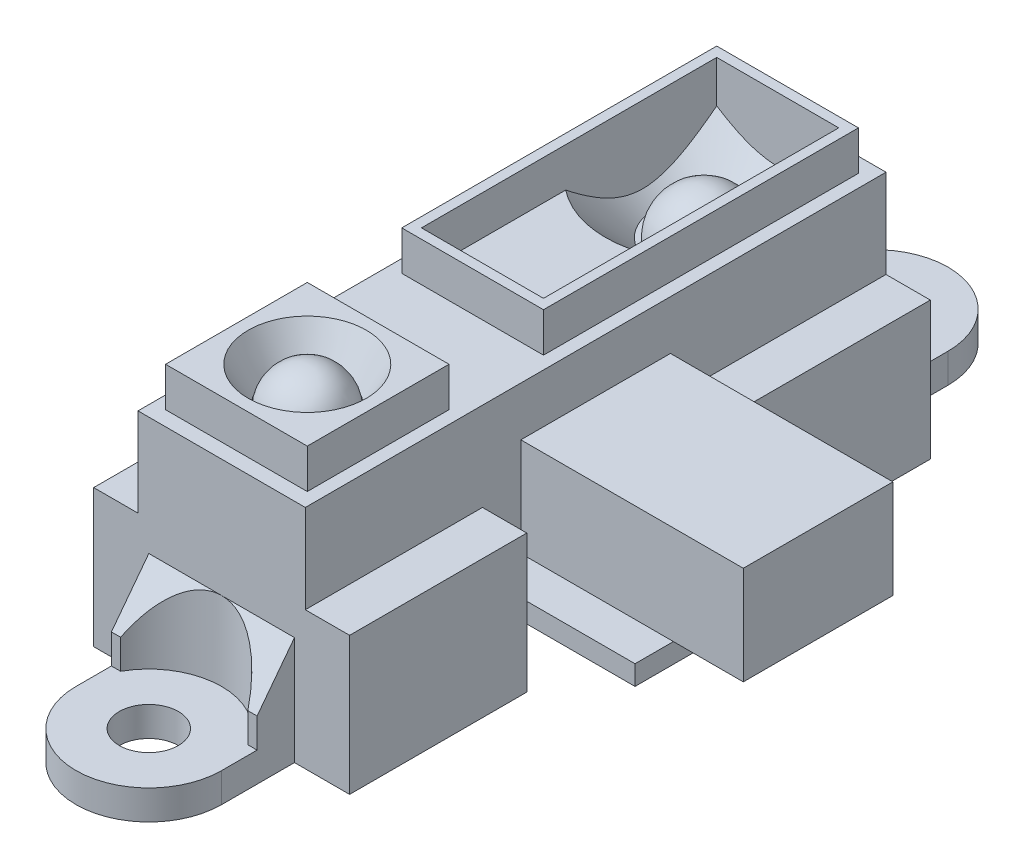
SolidWorks part; units mm, degrees
ref_plane "Спереди" through (0, 0, 0) normal (0, 0, 1) x (1, 0, 0)
ref_plane "Сверху" through (0, 0, 0) normal (0, 1, 0) x (1, 0, 0)
ref_plane "Справа" through (0, 0, 0) normal (1, 0, 0) x (0, 0, -1)
sketch "Эскиз1" plane through (0, 0, 0) normal (0, 1, 0) x (1, 0, 0)
  line L0 (0, 0) -> (13, 0)
  line L1 (13, 0) -> (13, 29.5)
  line L2 (13, 29.5) -> (0, 29.5)
  line L3 (0, 29.5) -> (0, 0)
extrude "Бобышка-Вытянуть1" add sketch "Эскиз1" along normal blind 7
sketch "Эскиз2" plane through (0, 7, 0) normal (0, 1, 0) x (1, 0, 0)
  line L0 (6.5, 29.5) -> (10.75, 29.5)
  line L1 (13, 29.5) -> (0, 29.5) construction
  line L2 (6.5, 29.5) -> (2.25, 29.5)
  line L3 (2.25, 29.5) -> (2.25, 0)
  line L4 (0, 0) -> (13, 0) construction
  line L5 (2.25, 0) -> (10.75, 0)
  line L6 (10.75, 0) -> (10.75, 29.5)
extrude "Бобышка-Вытянуть2" add sketch "Эскиз2" along normal blind 4.5
ref_plane "Плоскость1" through (6.5, 0, 0) normal (-1, 0, 0) x (0, 0, 1)
sketch "Эскиз5" plane through (6.5, 0, 0) normal (1, 0, 0) x (0, 0, -1)
  line L0 (29.5, 11.5) -> (24.5, 11.5)
  line L1 (0, 11.5) -> (29.5, 11.5) construction
  line L2 (24.5, 11.5) -> (24.5, 9) construction
  line L3 (24.5, 11.5) -> (24.5, 9) construction
  line L4 (26.75, 9) -> (27, 9)
  line L5 (24.5, 11.25) -> (24.5, 11.5)
  line L7 (27, 9) -> (29.5, 11.5)
  arc A0 (26.75, 9) -> (24.5, 11.25) centre (24.5, 9) ccw
  dimension "D1" = 5
revolve "Вырез-Повернуть2" cut sketch "Эскиз5" angle 360 about L2
sketch "Эскиз3" plane through (0, 11.5, 0) normal (0, 1, 0) x (1, 0, 0)
  line L1 (2.9, 7.95) -> (10.1, 0.75) construction
  line L2 (6.5, 29.5) -> (6.5, 28.75)
  line L3 (2.25, 0) -> (10.75, 0) construction
  line L4 (10.1, 7.95) -> (2.9, 0.75) construction
  line L5 (7.15, 20.75) -> (3.4, 20.75) construction
  line L6 (10.1, 0.75) -> (2.9, 0.75)
  line L7 (6.5, 6.325) -> (6.5, -6.325) construction
  line L10 (3.4, 20.75) -> (3.4, 28.25)
  line L11 (10.1, 12.75) -> (10.1, 28.75)
  line L12 (10.1, 0.75) -> (10.1, 0) construction
  line L13 (3.4, 28.25) -> (9.6, 28.25)
  line L14 (9.6, 28.25) -> (9.6, 13.25)
  line L15 (9.6, 13.25) -> (3.4, 13.25)
  line L16 (3.4, 13.25) -> (3.4, 20.75)
  line L17 (10.1, 0.75) -> (10.1, 7.95)
  line L18 (10.1, 7.95) -> (2.9, 7.95)
  line L19 (2.9, 7.95) -> (2.9, 0.75)
  line L20 (6.5, 29.5) -> (2.25, 29.5) construction
  line L21 (10.1, 28.75) -> (2.9, 28.75)
  line L22 (2.9, 28.75) -> (2.9, 12.75)
  line L23 (2.9, 12.75) -> (10.1, 12.75)
  circle A0 centre (6.5, 4.35) radius 2
  arc M19 (10.75, 21.8661) -> (2.25, 21.8661) centre (6.5, 24.5) cw
  dimension "D1" = 7.2
  dimension "D2" = 7.2
  dimension "D3" = 0.75
  dimension "D4" = 16
extrude "Бобышка-Вытянуть3" add sketch "Эскиз3" along normal blind 2 contours L22 L23 L11 L14 L15 L16 M19 | L21 L22 L16 L10 L13 L14 L11 M19 | L18 L19 L6 L17 A0 region at (6.5, 11.5, -0.8518) region at (3.3891, 11.5, -20.6635) region at (3.2903, 11.5, -16.9135)
sketch "Эскиз4" plane through (0, 11.5, 0) normal (0, 1, 0) x (1, 0, 0)
  line L0 (6.5, 4.35) -> (8.5, 4.35)
  line L1 (8.5, 4.35) -> (3.7, 4.35)
  circle A0 centre (6.5, 4.35) radius 2 construction
  arc A2 (8.5, 4.35) -> (4.5, 4.35) centre (6.5, 4.35) ccw
revolve "Повернуть1" add sketch "Эскиз4" angle 360 about L0 region at (6.5, 11.5, -5.1988)
chamfer "Фаска1" distance 1 angle 60 1 edges at (6.5, 13.5, -2.35) first distance on face at (6.5, 13.5, -2.35)
sketch "Эскиз7" plane through (0, 11.5, 0) normal (0, 1, 0) x (1, 0, 0)
  line L0 (2.25, 29.5) -> (10.75, 29.5)
  line L3 (10.75, 27.1339) -> (10.75, 29.5) construction
  line L4 (10.75, 28.25) -> (10.75, 29.5)
  line L5 (9.6, 28.25) -> (3.4, 28.25)
  line L6 (2.25, 29.5) -> (2.25, 0) construction
  line L7 (2.25, 28.25) -> (2.25, 29.5)
  line L8 (3.4, 28.25) -> (3.4, 20.1869)
  line L9 (3.4, 13.25) -> (3.4, 28.25) construction
  line L10 (3.4, 20.1869) -> (2.25, 20.1869)
  line L11 (2.25, 20.1869) -> (2.25, 28.25)
  line L12 (10.75, 28.25) -> (10.75, 20.1869)
  line L13 (10.75, 0) -> (10.75, 21.8661) construction
  line L14 (10.75, 20.1869) -> (9.6, 20.1869)
  line L15 (9.6, 20.577) -> (9.6, 13.25) construction
  line L16 (9.6, 20.1869) -> (9.6, 28.25)
extrude "Бобышка-Вытянуть4" add sketch "Эскиз7" against normal blind 2
sketch "Эскиз8" plane through (0, 0, 0) normal (0, -1, 0) x (-1, 0, 0)
  line L0 (-6.5, 0) -> (-6.5, -7.4) construction
  line L1 (0, 0) -> (-13, 0) construction
  line L2 (-6.5, -6.325) -> (-6.5, 6.325) construction
  line L3 (-2.8, -3.7) -> (-2.8, 0)
  line L4 (-10.2, -3.7) -> (-10.2, 0)
  line L5 (-10.2, 0) -> (-2.8, 0)
  arc A0 (-10.2, -3.7) -> (-2.8, -3.7) centre (-6.5, -3.7) ccw
  circle A1 centre (-6.5, -3.7) radius 1.5
extrude "Бобышка-Вытянуть5" add sketch "Эскиз8" against normal blind 5.5
sketch "Эскиз9" plane through (0, 0, 0) normal (-1, 0, 0) x (0, 0, 1)
  line L0 (7.4, 0) -> (7.4, 1.5)
  line L1 (7.4, 0) -> (7.4, 5.5) construction
  line L2 (0, 5.5) -> (7.4, 8.098)
  line L4 (7.4, 1.5) -> (1.9, 1.5)
  line L5 (1.9, 1.5) -> (1.9, 3)
  line L6 (1.9, 3) -> (0, 5.5)
  line L7 (7.4, 8.098) -> (10.7855, 4.1441)
  line L8 (10.7855, 4.1441) -> (7.4, 1.5)
extrude "Вырез-Вытянуть1" cut sketch "Эскиз9" against normal through all contours L8 L7 L2 L6 L5 L4 region at (0, 4.4387, 5.4916)
sketch "Эскиз10" plane through (0, 1.5, 0) normal (0, 1, 0) x (1, 0, 0)
  circle A0 centre (6.5, -3.7) radius 3.7
extrude "Вырез-Вытянуть2" cut sketch "Эскиз10" along normal blind 5.5
ref_plane "Плоскость2" through (0, 0, -14.75) normal (0, 0, -1) x (-1, 0, 0)
mirror "Зеркальное отражение1" about plane through (0, 0, -14.75) normal (0, 0, -1) of "Бобышка-Вытянуть1", "Вырез-Вытянуть2", "Бобышка-Вытянуть5", "Вырез-Вытянуть1"
sketch "Эскиз11" plane through (0, 0, 0) normal (0, -1, 0) x (-1, 0, 0)
  line L3 (-12.5, 9) -> (-12.5, 0.5)
  line L4 (-12.5, 0.5) -> (-0.5, 0.5)
  line L5 (-0.5, 0.5) -> (-0.5, 29)
  line L6 (-0.5, 29) -> (-12.5, 29)
  line L7 (-12.5, 29) -> (-12.5, 20.5)
  line L10 (-12.5, 20.5) -> (-15.1831, 20.5)
  line L11 (-15.1831, 20.5) -> (-15.1831, 9)
  line L12 (-15.1831, 9) -> (-12.5, 9)
extrude "Вырез-Вытянуть3" cut sketch "Эскиз11" against normal blind 3
sketch "Эскиз12" plane through (0, 3, 0) normal (0, -1, 0) x (-1, 0, 0)
  line L0 (-13, 9) -> (-10.75, 9)
  line L1 (-10.75, 0) -> (-10.75, 29.5) construction
  line L2 (-13, 9) -> (-13, 20.5)
  line L3 (-13, 20.5) -> (-10.75, 20.5)
  line L4 (-10.75, 20.5) -> (-10.75, 9)
  line M1 (-13, 20.5) -> (-13, 9)
  line M2 (-13, 9) -> (-12.5, 9)
  line M8 (-12.5, 20.5) -> (-13, 20.5)
extrude "Вырез-Вытянуть4" cut sketch "Эскиз12" against normal through all contours L4 L3 L0 M8 M1 M2 region at (11.875, 3, -14.75)
sketch "Эскиз13" plane through (0, 3, 0) normal (0, -1, 0) x (-1, 0, 0)
  line L0 (-10.75, 9) -> (-10.75, 20.5)
  line L1 (-10.75, 20.5) -> (-13, 20.5)
  line L2 (-13, 20.5) -> (-18.5, 20.5)
  line L3 (-18.5, 20.5) -> (-18.5, 9)
  line L4 (-18.5, 9) -> (-10.75, 9)
extrude "Бобышка-Вытянуть6" add sketch "Эскиз13" against normal blind 1
sketch "Эскиз14" plane through (0, 4, 0) normal (0, 1, 0) x (1, 0, 0)
  line L0 (18.5, 14.75) -> (18.5, 18.55) construction
  line L1 (18.5, 20.5) -> (18.5, 9) construction
  line L2 (18.5, 18.55) -> (10.75, 18.55)
  line L3 (10.75, 0) -> (10.75, 29.5) construction
  line L4 (10.75, 18.55) -> (10.75, 10.95)
  line L5 (10.75, 10.95) -> (22.05, 10.95)
  line L6 (22.05, 10.95) -> (22.05, 18.55)
  line L7 (22.05, 18.55) -> (18.5, 18.55)
  line L8 (10.75, 18.55) -> (10.75, 10.95)
  line M2 (18.5, 9) -> (18.5, 20.5)
  line M5 (10.75, 20.5) -> (10.75, 9)
extrude "Бобышка-Вытянуть7" add sketch "Эскиз14" along normal blind 5 contours L5 L2 M5 M2 | L6 L7 L5 M2 region at (14.625, 4, -14.75) region at (20.275, 4, -14.75)
sketch "Эскиз15" plane through (0, 0, 0) normal (1, 0, 0) x (0, 0, -1)
  line L0 (14.75, 11.5) -> (14.75, -12.5)
  line L1 (0, 11.5) -> (29.5, 11.5) construction
  line L3 (14.75, 11.5) -> (14.75, 13.5)
  line L4 (14.75, 13.5) -> (56.0482, 13.5) construction
  line L5 (14.75, -12.5) -> (0.75, 13.5)
  line L6 (14.75, -12.5) -> (-52.9823, 13.5)
  circle A0 centre (14.75, -12.5) radius 28
  circle A1 centre (14.75, -12.5) radius 26
  dimension "D1" = 28.301
  dimension "D2" = 69
sketch "Эскиз16" plane through (0, 0, -29.5) normal (0, 0, -1) x (-1, 0, 0)
  line L0 (-6.5, 11.5) -> (-6.5, -11.5)
  line L1 (-10.75, 11.5) -> (-2.25, 11.5) construction
  line L2 (-6.5, -1.5) -> (-12.5, -1.5)
  line L3 (-22.05, 8.3374) -> (-22.05, 10.3374)
  line L4 (-22.05, 9) -> (-22.05, 4) construction
  line L5 (-22.05, 10.3374) -> (-10.75, 11.5)
  line L6 (-6.5, -11.5) -> (-6.5, -1.5)
  line L7 (-6.5, -11.5) -> (-6.5, -1.5)
  circle A0 centre (-6.5, -11.5) radius 11.6619
  dimension "D1" = 10
  dimension "D2" = 13
sketch "Эскиз17" plane through (10.75, 0, 0) normal (1, 0, 0) x (0, 0, -1)
  line L0 (18.55, 9) -> (10.95, 9) construction
  circle A0 centre (14.75, -12.5) radius 28 construction
  ellipse E0 centre (14.75, -12.5) end of major axis (-13.25, -12.5) minor radius 24
  ellipse E1 centre (14.75, -12.5) end of major axis (-11.25, -12.5) minor radius 21.5
sketch "Эскиз18" plane through (0, 11.5, 0) normal (0, 1, 0) x (1, 0, 0)
  line L0 (0, 29.5) -> (0, 0) construction
  line L1 (0, 0) -> (0, 14.75)
  line L2 (13, 29.5) -> (13, 0) construction
  line L3 (13, 14.75) -> (0, 14.75) construction
  line L4 (2.25, 29.5) -> (10.75, 29.5)
  line L5 (10.75, 29.5) -> (10.75, 0)
  line L6 (10.75, 0) -> (2.25, 0)
  line L7 (2.25, 0) -> (2.25, 29.5)
  line L8 (6.5, 36.9) -> (10.75, 36.9)
  line L9 (10.75, -13.25) -> (10.75, 42.75) construction
  line L10 (10.75, 36.9) -> (2.25, 36.9)
  line L11 (2.25, 36.9) -> (2.25, 29.5)
  line L12 (6.5, -7.4) -> (2.8, -7.4) construction
  line L13 (2.25, 0) -> (2.25, -7.4)
  line L14 (10.75, 0) -> (10.75, -7.4)
  line L15 (10.75, -7.4) -> (2.25, -7.4)
  line L16 (10.75, 20.5) -> (24.75, 20.5)
  line L17 (24.75, 20.5) -> (24.75, 9)
  line L18 (24.75, 9) -> (10.75, 9)
  line L19 (10.75, 9) -> (13, 9) construction
  arc A0 (10.2, 33.2) -> (2.8, 33.2) centre (6.5, 33.2) ccw construction
